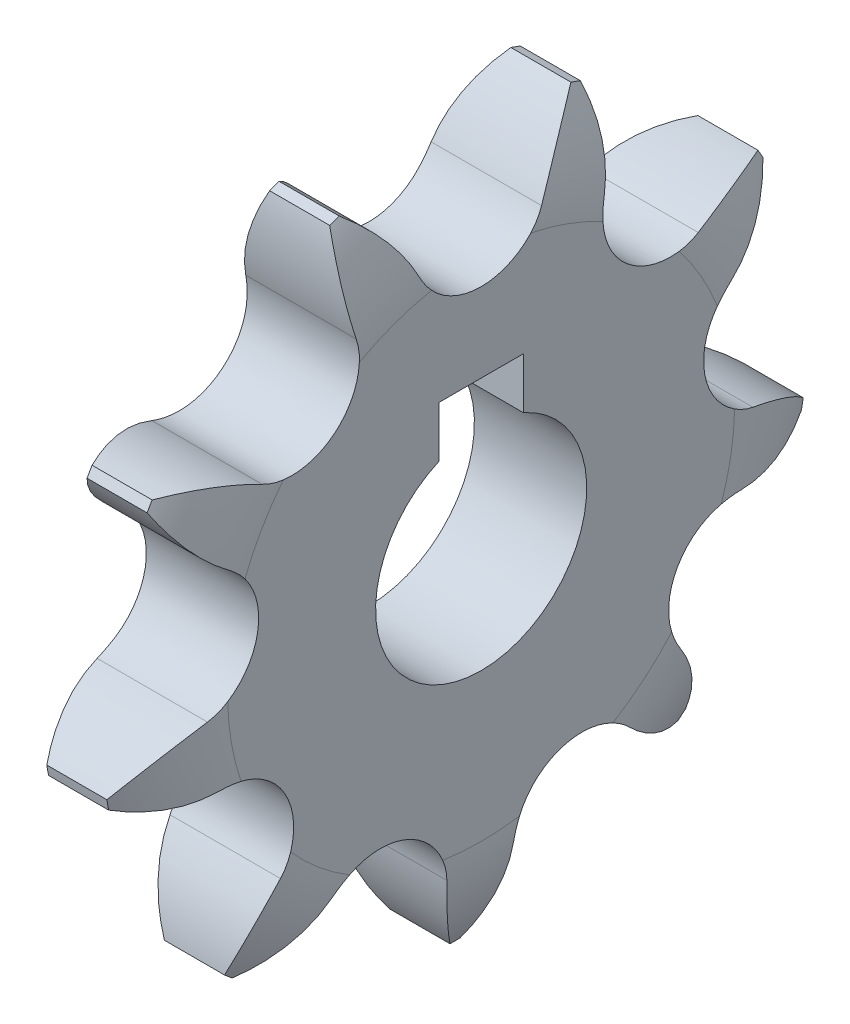
SolidWorks part; units mm, degrees
ref_plane "Plane1" through (0, 0, 0) normal (0, 0, 1) x (1, 0, 0)
ref_plane "Plane2" through (0, 0, 0) normal (0, 1, 0) x (1, 0, 0)
ref_plane "Plane3" through (0, 0, 0) normal (1, 0, 0) x (0, 0, -1)
sketch "Clipboard" plane through (0, 0, 0) normal (0, 1, 0) x (1, 0, 0)
  line L0 (0, 0) -> (9.4077, -1.49)
  line L1 (-15, 0) -> (100, 0) construction
  line L2 (0, 0) -> (-0.8203, 0.9272)
  line L3 (0, 0) -> (-8.8973, 3.4006)
  line L4 (0, 0) -> (3.0618, 0.4849)
  line L5 (0, 0) -> (-46.8476, -17.4728)
  line L6 (0, 0) -> (-4.4098, -2.9753)
  line L7 (-0.8203, 0.9272) -> (48.4205, 9.6097)
  line L8 (-76.2, 38.1) -> (-74.4, 38.1)
  line L9 (-73.3242, 40.7328) -> (-72.926, 40.7699)
  line L10 (-73.4529, 9.1872) -> (-63.2129, 9.1872)
  circle A0 centre (0, 0) radius 3.175
  circle A1 centre (0, 0) radius 8.4097
  circle A2 centre (0, 0) radius 37.5
  dimension "Num_teeth" = 9
  dimension "Thickness" = 5.3196
sketch "BasProSke" plane through (0, 0, 0) normal (0, 1, 0) x (1, 0, 0)
  line L0 (-10, 0) -> (60, 0) construction
  line L1 (0, 0) -> (0, 12.0069)
  line L2 (0, 0) -> (5.3196, 0)
  line L3 (5.3196, 0) -> (5.3196, 12.0069)
  line L4 (4.0816, 16.7027) -> (1.238, 16.7027)
  arc A0 (0, 12.0069) -> (1.238, 16.7027) centre (9.525, 12.0069) cw
  arc A1 (5.3196, 12.0069) -> (4.0816, 16.7027) centre (-4.2054, 12.0069) ccw
  dimension "D1" = 9.525
  dimension "Thickness" = 5.3196
  dimension "Diameter" = 33.4055
revolve "Base-Revolve" add sketch "BasProSke" angle 360 about L0
sketch "TooCutSke" plane through (0, 0, 0) normal (1, 0, 0) x (0, 0, -1)
  line L0 (0, 13.9564) -> (2.9063, 12.6011) construction
  line L1 (0, 0) -> (0, 107) construction
  line L2 (0, 13.9564) -> (-10, 13.9564) construction
  line L3 (0, 13.9564) -> (-2.9063, 12.6011) construction
  arc A0 (2.9063, 12.6011) -> (5.9941, 16.1247) centre (10.503, 9.0588) cw
  arc A1 (2.9063, 12.6011) -> (-2.9063, 12.6011) centre (0, 13.9564) cw
  arc A2 (-2.9063, 12.6011) -> (-5.9941, 16.1247) centre (-10.503, 9.0588) ccw
  arc A3 (5.9941, 16.1247) -> (-5.9941, 16.1247) centre (0, 0) ccw
extrude "ToothCut" cut sketch "TooCutSke" along normal through all
pattern_circular "TeethCuts" count 9 every 40 about axis through (-10, 0, 0) along (1, 0, 0) of "ToothCut"
sketch "HubNeaOneSke" plane through (0, 0, 0) normal (-1, 0, 0) x (0, 0, 1)
  circle A0 centre (0, 0) radius 8.4097
  dimension "Diameter" = 16.8193
extrude "HubNearOne" [suppressed] add sketch "HubNeaOneSke" along normal blind 44.6809
fillet "HubNearOneFillet" [suppressed] radius 0.4
sketch "HubNeaBotSke" plane through (0, 0, 0) normal (-1, 0, 0) x (0, 0, 1)
  circle A0 centre (0, 0) radius 8.4097
  dimension "Diameter" = 16.8193
extrude "HubNearBoth" [suppressed] add sketch "HubNeaBotSke" along normal blind 22.3405
fillet "HubNearBothFillet" [suppressed] radius 0.4
ref_plane "FarPln" through (5.3196, 0, 0) normal (1, 0, 0) x (0, 0, -1)
sketch "HubFarSke" plane through (5.3196, 0, 0) normal (1, 0, 0) x (0, 0, -1)
  circle A0 centre (0, 0) radius 8.4097
  dimension "Diameter" = 16.8193
extrude "HubFar" [suppressed] add sketch "HubFarSke" along normal blind 22.3405
fillet "HubFarFillet" [suppressed] radius 0.4
sketch "BorSke" plane through (0, 0, 0) normal (1, 0, 0) x (0, 0, -1)
  circle A0 centre (0, 0) radius 5
  dimension "Diameter" = 10
extrude "Bore" cut sketch "BorSke" along normal mid plane 100.001
sketch "KeySke" plane through (0, 0, 0) normal (1, 0, 0) x (0, 0, -1)
  line L0 (-2, 0) -> (-2, 6.8)
  line L1 (-2, 6.8) -> (2, 6.8)
  line L2 (2, 6.8) -> (2, 0)
  line L3 (0, 0) -> (0, 34) construction
  line L4 (-2, 0) -> (2, 0)
  dimension "Width" = 4
extrude "Keyway" [suppressed] cut sketch "KeySke" along normal mid plane 100.001
pattern_circular "Keyway2" [suppressed] count 2 every 90 about axis through (-10, 0, 0) along (1, 0, 0)
sketch "Sketch1" plane through (5.3196, 0, 0) normal (1, 0, 0) x (0, 0, -1)
  circle A0 centre (0, 0) radius 9
  circle A1 centre (0, 0) radius 3
  dimension "D1" = 18
  dimension "D2" = 6
extrude "Boss-Extrude1" add sketch "Sketch1" along normal offset from surface (16.6804 mm away) 22 up to face at (0, 0, -5)
sketch "Sketch2" plane through (0, 0, 0) normal (1, 0, 0) x (0, 0, -1)
  circle A0 centre (0, 0) radius 5
  dimension "D1" = 10
extrude "Cut-Extrude1" cut sketch "Sketch2" along normal blind 24
sketch "Sketch3" plane through (0, 0, 0) normal (-1, 0, 0) x (0, 0, 1)
  line L0 (-2, 7) -> (-2, 3)
  line L1 (-2, 7) -> (2, 7)
  line L2 (-2, 3) -> (2, 3)
  line L3 (2, 7) -> (2, 3)
  line L4 (-2, 7) -> (2, 3) construction
  line L5 (-2, 3) -> (2, 7) construction
  line L6 (0, 0) -> (0, 5) construction
  circle A0 centre (0, 0) radius 5 construction
  point P1 (0, 5)
  dimension "D1" = 4
  dimension "D2" = 4
extrude "Cut-Extrude2" cut sketch "Sketch3" against normal through all
sketch "Sketch4" plane through (22, 0, 0) normal (1, 0, 0) x (0, 0, -1)
  circle A0 centre (0, 0) radius 12.1759
extrude "Cut-Extrude3" cut sketch "Sketch4" against normal up to surface (16.6804 mm away) up to face at (5.3196, 0, 9)
equation "' \"Pitch@Clipboard\" = 12.7"
equation "' \"Num_strands@Clipboard\" = 1"
equation "' \"Num_teeth@Clipboard\" = 9"
equation "' \"Hub_dia@Clipboard\" = 50"
equation "' \"Overall_len@Clipboard\" = 3"
equation "' \"Diameter@BorSke\" = 12"
equation "' \"T_dim@Clipboard\" = 1"
equation "' \"Width@KeySke\" = 2"
equation "' \"Dr@Clipboard\" = 8.51"
equation "' \"Face_width@Clipboard\" = 7.2"
equation "' \"Side_radius@Clipboard\" = 12.7"
equation "' \"Side_relief@Clipboard\" = 1.27"
equation "' \"Transv_pitch@Clipboard\" = 13.92"
equation "' \"Show_teeth@Clipboard\" = 9"
equation "' \"Fillet_rad@Clipboard\" = 0.6"
equation "' \"Plate_wid@Clipboard\" = 11.8"
equation "\"Num_teeth@Clipboard\" = int( \"Num_teeth@Clipboard\" )"
equation "\"Num_teeth@Clipboard\" = ((sgn( \"Num_teeth@Clipboard\" - 5.0)+1)*( \"Num_teeth@Clipboard\" - 5.0))/2 +5.0"
equation "\"Num_teeth@Clipboard\" = ((sgn( \"Num_teeth@Clipboard\" - 200.0)-1)*( \"Num_teeth@Clipboard\" - 200.0))/-2 +200.0"
equation "\"MHD@Clipboard\" = \"Pitch@Clipboard\" * (1.0 / tan(3.14159265 / \"Num_teeth@Clipboard\" )) - 1.04 * \"Plate_wid@Clipboard\" - 0.76"
equation "\"Thickness@Clipboard\"  = \"Face_width@Clipboard\" + (\"Num_strands@Clipboard\" - 1) * \"Transv_pitch@Clipboard\""
equation "\"OAL@Clipboard\" = \"Thickness@Clipboard\" + 2 * \"Fillet_rad@Clipboard\" + 1"
equation "\"MHD@Clipboard\" = ((sgn( \"MHD@Clipboard\" - \"Hub_dia@Clipboard\" )-1)*( \"MHD@Clipboard\" - \"Hub_dia@Clipboard\" ))/-2+ \"Hub_dia@Clipboard\""
equation "\"OAL@Clipboard\" = ((sgn( \"OAL@Clipboard\" - \"Overall_len@Clipboard\" )+1)*( \"OAL@Clipboard\" - \"Overall_len@Clipboard\" ))/2 + \"Overall_len@Clipboard\" + 0.0005"
equation "\"Num_teeth@TeethCuts\" = int( \"Show_teeth@Clipboard\" ) + 1"
equation "\"Num_teeth@TeethCuts\" = ((sgn( \"Num_teeth@TeethCuts\" - \"Num_teeth@Clipboard\" )-1)*( \"Num_teeth@TeethCuts\" - \"Num_teeth@Clipboard\" ))/-2+ \"Num_teeth@Clipboard\""
equation "\"Num_teeth@TeethCuts\" = ((sgn( \"Num_teeth@TeethCuts\" - 2.0)+1)*( \"Num_teeth@TeethCuts\" - 2.0))/2 +2.0"
equation "\"Angle@TeethCuts\" = 360.0 / \"Num_teeth@Clipboard\""
equation "\"Seat_radius@TooCutSke\" = ( \"Pitch@Clipboard\" / 2.0) / sin(3.14159265 / \"Num_teeth@Clipboard\" ) - \"Dr@Clipboard\" / 2.0 + \"Dr@Clipboard\" * 0.505"
equation "\"R1@TooCutSke\"  = \"Dr@Clipboard\" * 0.505"
equation "\"X@TooCutSke\" = 140.0 - (90.0 / \"Num_teeth@Clipboard\")"
equation "\"R2@TooCutSke\" = 0.12 * \"Dr@Clipboard\" * ( \"Num_teeth@Clipboard\" + 2.0)"
equation "\"Overcut@TooCutSke\" = 0.5 + 0.625 * \"Pitch@Clipboard\" - 0.5 * \"Dr@Clipboard\"  +  \"Pitch@Clipboard\" / 2.0 / sin(3.14159265 / \"Num_teeth@Clipboard\" )"
equation "\"Diameter@BasProSke\" = 2.0 * ( 0.625 * \"Pitch@Clipboard\" - 0.5 * \"Dr@Clipboard\"  +  \"Pitch@Clipboard\" / 2.0 / sin(3.14159265 / \"Num_teeth@Clipboard\" ))"
equation "\"Thickness@BasProSke\"  = \"Thickness@Clipboard\""
equation "\"G1@BasProSke\" =  \"Side_relief@Clipboard\""
equation "\"G2@BasProSke\" =  \"Side_relief@Clipboard\""
equation "\"D1@BasProSke\" =  \"Side_radius@Clipboard\""
equation "\"Diameter@HubNeaOneSke\" = \"MHD@Clipboard\""
equation "\"Length@HubNearOne\" = \"OAL@Clipboard\" - \"Thickness@BasProSke\""
equation "\"Diameter@HubNeaBotSke\" = \"MHD@Clipboard\""
equation "\"Length@HubNearBoth\" = ( \"OAL@Clipboard\" - \"Thickness@BasProSke\" ) / 2.0"
equation "\"D1@HubNearOneFillet\" = \"Fillet_rad@Clipboard\""
equation "\"D1@HubNearBothFillet\" = \"Fillet_rad@Clipboard\""
equation "\"Thickness@FarPln\" = \"Thickness@BasProSke\""
equation "\"Diameter@HubFarSke\" = \"MHD@Clipboard\""
equation "\"Length@HubFar\" = ( \"OAL@Clipboard\" - \"Thickness@BasProSke\" ) / 2.0"
equation "\"D1@HubFarFillet\" = \"Fillet_rad@Clipboard\""
equation "\"D1@Bore\" = \"OAL@Clipboard\" * 2.0"
equation "\"D1@Keyway\" = \"OAL@Clipboard\" * 2.0"
equation "\"Offset@KeySke\" = \"T_dim@Clipboard\" + \"Diameter@BorSke\" / 2.0"
